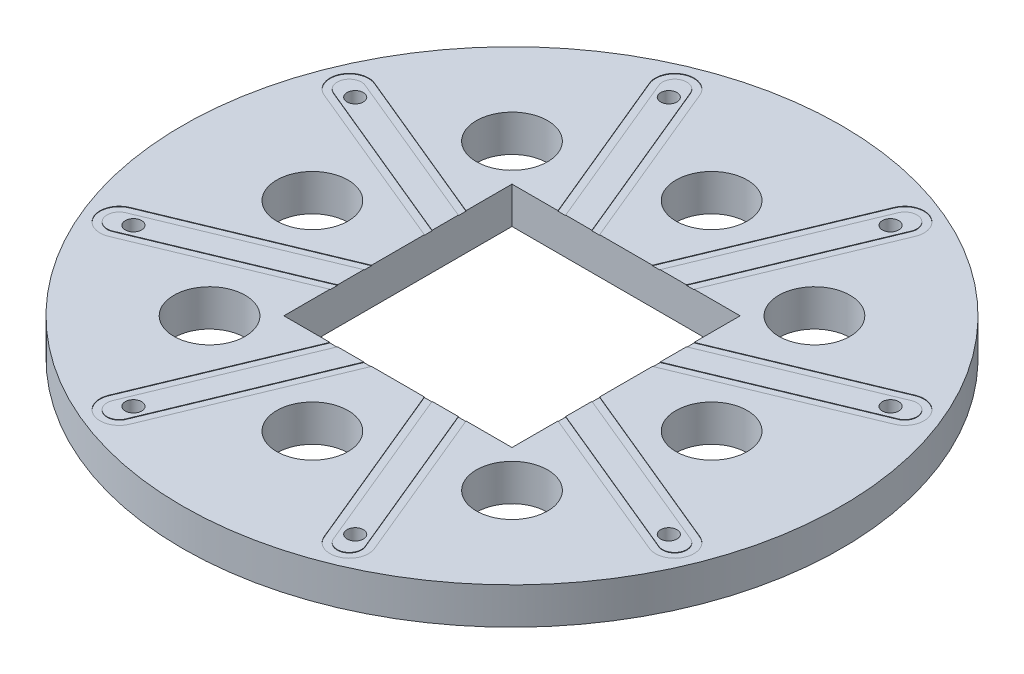
SolidWorks part; units mm, degrees
material "Ceramic Porcelain"
ref_plane "Front Plane" through (0, 0, 0) normal (0, 0, 1) x (1, 0, 0)
ref_plane "Top Plane" through (0, 0, 0) normal (0, 1, 0) x (1, 0, 0)
ref_plane "Right Plane" through (0, 0, 0) normal (1, 0, 0) x (0, 0, -1)
ref_axis "Y Axis" through (0, 0.0762, 0) along (0, -1, 0)
sketch "Boday Sketch" plane through (0, 0, 0) normal (0, 1, 0) x (1, 0, 0)
  circle A0 centre (0, 0) radius 11.557
  dimension "D1" = 23.114
extrude "Body" add sketch "Boday Sketch" against normal blind 1.27
sketch "Copper Sketch" plane through (0, 0, 0) normal (0, 1, 0) x (1, 0, 0)
  circle A0 centre (0, 0) radius 11.557
  dimension "D1" = 23.114
extrude "Copper" add sketch "Copper Sketch" along normal blind 0.0175
sketch "IO Hole Positions" plane through (0, 0, 0) normal (0, 1, 0) x (1, 0, 0)
  point P0 (-3.8881, 9.3866)
  point P1 (3.8881, 9.3866)
  point P5 (9.3866, 3.8881)
  point P6 (9.3866, -3.8881)
  point P7 (3.8881, -9.3866)
  point P8 (-3.8881, -9.3866)
  point P9 (-9.3866, -3.8881)
  point P10 (-9.3866, 3.8881)
  point P11 (0, 0)
  dimension "D1" = 10.16
  dimension "D2" = 8
sketch "Gap" plane through (0, 0, 0) normal (0, 1, 0) x (1, 0, 0)
  line L1 (0.6236, 0.2583) -> (-3.4102, 9.9969)
  line L2 (-4.6575, 9.4803) -> (-0.6236, -0.2583)
  line L3 (-0.6236, -0.2583) -> (0.6236, 0.2583)
  arc A0 (-3.4102, 9.9969) -> (-4.6575, 9.4803) centre (-4.0339, 9.7386) ccw
  point P0 (0.6236, 0.2583)
sketch "Center Sketch" plane through (0, 0, 0) normal (0, 1, 0) x (1, 0, 0)
  line L0 (0.3926, 0.1626) -> (-3.6412, 9.9013)
  line L1 (-4.4265, 9.576) -> (-0.3926, -0.1626)
  line L2 (-0.3926, -0.1626) -> (0.3926, 0.1626)
  arc A0 (-3.6412, 9.9013) -> (-4.4265, 9.576) centre (-4.0339, 9.7386) ccw
  point P0 (0.3926, 0.1626)
  point P3 (-3.6412, 9.9013)
  dimension "D1" = 0.425
extrude "Gap Cut" cut sketch "Gap" along normal through all
extrude "Center" add sketch "Center Sketch" along normal blind 0.0175 separate body
sketch "IO Hole Sketch" plane through (0, 0, 0) normal (0, 1, 0) x (1, 0, 0)
  circle A0 centre (-3.8881, 9.3866) radius 0.287
  dimension "D1" = 0.574
extrude "IO Hole" cut sketch "IO Hole Sketch" against normal through all and the other way through all
pattern_circular "Gap Cuts" count 8 over 360 about axis through (0, 0.0762, 0) along (0, -1, 0) of "Gap Cut"
pattern_circular "Centers" count 8 over 360 about axis through (0, 0.0762, 0) along (0, -1, 0) of "Center"
pattern_circular "IO Holes" count 8 over 360 about axis through (0, 0.0762, 0) along (0, -1, 0) of "IO Hole"
sketch "Pocket Sketch" plane through (0, 0, 0) normal (0, 1, 0) x (1, 0, 0)
  line L1 (-4, -4) -> (4, -4)
  line L2 (-4, -4) -> (-4, 4)
  line L3 (-4, 4) -> (4, 4)
  line L4 (4, -4) -> (4, 4)
  line L5 (-4, -4) -> (4, 4) construction
  line L6 (-4, 4) -> (4, -4) construction
  point P0 (0, 0)
  dimension "D2" = 8
  dimension "D1" = 8
extrude "Pocket" cut sketch "Pocket Sketch" against normal through all and the other way through all
sketch "Posts" plane through (0, 0, 0) normal (0, 1, 0) x (1, 0, 0)
  circle A0 centre (0, 7) radius 1.25
  circle A8 centre (-5.3033, 5.3033) radius 1.25
  point P0 (0, 7)
  point P4 (-5.3033, 5.3033)
  dimension "D2" = 2.5
  dimension "D4" = 2.5
  dimension "D1" = 7
  dimension "D3" = 7.5
extrude "Post Cut" cut sketch "Posts" against normal through all and the other way through all
pattern_circular "Post Cuts" count 4 over 360 about axis through (0, 0.0762, 0) along (0, -1, 0) of "Post Cut"
equation "\"mount_d\"= 0.91in"
equation "\"dieletric_h\"= 0.05in"
equation "\"D1@Boday Sketch\" = \"mount_d\""
equation "\"D1@Body\" = \"dieletric_h\""
equation "\"screw_inner_r\"= 0.415in"
equation "\"io_r\"= 0.4in"
equation "\"D1@IO Hole Positions\" = \"io_r\""
equation "\"io_hole_d\"= 0.574mm"
equation "\"D1@IO Hole Sketch\" = \"io_hole_d\""
equation "\"W\"= 0.85mm"
equation "\"G\"= 0.25mm"
equation "\"copper_t\"= 17.5um"
equation "\"D1@Gap\"=\"W\" / 2 + \"G\""
equation "\"silicon_size\"= 8mm"
equation "\"D1@Center\" = \"copper_t\""
equation "\"D1@Copper\"=\"copper_t\""
equation "\"D1@Pocket Sketch\" = \"silicon_size\""
equation "\"D2@Pocket Sketch\" = \"silicon_size\""
equation "\"post_r1\"= 7mm"
equation "\"post_r2\"= 7.5mm"
equation "\"D1@Posts\"=\"post_r1\""
equation "\"post_size\"= 2.5mm"
equation "\"D2@Posts\"=\"post_size\""
equation "\"D3@Posts\"=\"post_r2\""
equation "\"D4@Posts\"=\"post_size\""
